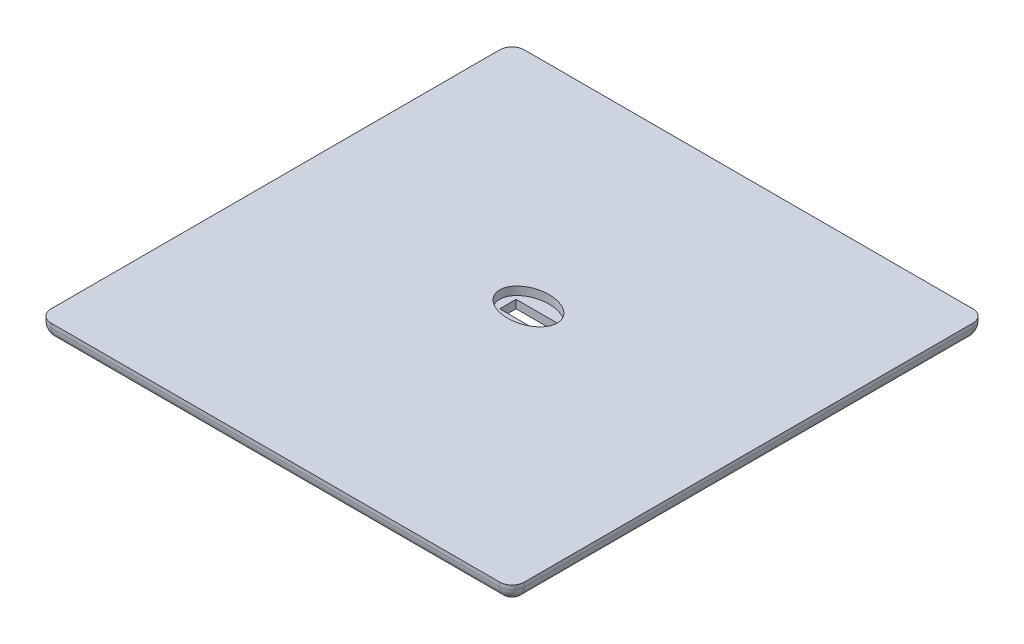
SolidWorks part; units mm, degrees
ref_plane "Front Plane" through (0, 0, 0) normal (0, 0, 1) x (1, 0, 0)
ref_plane "Top Plane" through (0, 0, 0) normal (0, 1, 0) x (1, 0, 0)
ref_plane "Right Plane" through (0, 0, 0) normal (1, 0, 0) x (0, 0, -1)
sketch "Sketch7" plane through (0, 0, 0) normal (0, 0, 1) x (1, 0, 0)
  line L0 (55, 0) -> (-55, 0) construction
  line L1 (-47.5, 4) -> (47.5, 4)
  line L2 (-47.5, 4) -> (-47.5, 0)
  line L3 (-47.5, 0) -> (47.5, 0)
  line L4 (47.5, 4) -> (47.5, 0)
  point P6 (0, 0)
  point P7 (0, 0)
  point P8 (0, 0)
  point P9 (0, 0)
  point P10 (0, 0)
  point P11 (0, 0)
extrude "Boss-Extrude4" add sketch "Sketch7" along normal blind 47.5 and the other way blind 47.5
sketch "Sketch8" plane through (0, 0, 0) normal (0, 0, 1) x (1, 0, 0)
  line L1 (-52.5, 4) -> (52.5, 4)
  line L2 (-52.5, 4) -> (-52.5, 8)
  line L3 (-52.5, 8) -> (52.5, 8)
  line L4 (52.5, 4) -> (52.5, 8)
  point P4 (0, 0)
  point P5 (0, 0)
  point P6 (0, 0)
  point P7 (0, 0)
  point P8 (0, 0)
  point P9 (0, 0)
  point P10 (0, 0)
extrude "Boss-Extrude5" add sketch "Sketch8" along normal blind 52.5 and the other way blind 52.5
sketch "Sketch9" plane through (0, 0, 0) normal (0, 0, 1) x (1, 0, 0)
  line L1 (-57.5, 12) -> (57.5, 12)
  line L2 (-57.5, 12) -> (-57.5, 8)
  line L3 (-57.5, 8) -> (57.5, 8)
  line L4 (57.5, 12) -> (57.5, 8)
  point P4 (0, 0)
  point P5 (0, 0)
  point P6 (0, 0)
  point P7 (0, 0)
  point P8 (0, 0)
  point P9 (0, 0)
  point P10 (0, 0)
  point P11 (0, 0)
  point P12 (0, 0)
  point P13 (0, 0)
extrude "Boss-Extrude6" add sketch "Sketch9" along normal blind 57.5 and the other way blind 57.5
sketch "Sketch10" plane through (0, 0, 0) normal (0, 1, 0) x (1, 0, 0)
  line L1 (-42.5, 42.5) -> (42.5, 42.5)
  line L2 (-42.5, 42.5) -> (-42.5, -42.5)
  line L3 (-42.5, -42.5) -> (42.5, -42.5)
  line L4 (42.5, 42.5) -> (42.5, -42.5)
  point P4 (0, 0)
  point P5 (0, 0)
  point P6 (0, 0)
extrude "Cut-Extrude1" cut sketch "Sketch10" against normal blind 3.5 and the other way blind 8
sketch "Sketch12" plane through (0, 12, 0) normal (0, 1, 0) x (1, 0, 0)
  ellipse E0 centre (0, 4) end of major axis (7, 4) minor radius 5
extrude "Cut-Extrude2" cut sketch "Sketch12" against normal blind 2
sketch "Sketch13" plane through (0, 0, 0) normal (0, 1, 0) x (1, 0, 0)
  line L1 (-5, 6) -> (5, 6)
  line L2 (-5, 6) -> (-5, 2)
  line L3 (-5, 2) -> (5, 2)
  line L4 (5, 6) -> (5, 2)
  point P4 (0, 0)
  point P5 (0, 0)
  point P6 (0, 0)
  point P7 (0, 0)
extrude "Cut-Extrude3" cut sketch "Sketch13" against normal through all and the other way blind 29
fillet "Fillet4" radius 3 24 edges at (-47.5, 2, -47.5) (-52.5, 6, -52.5) (-57.5, 10, -57.5) (-47.5, 0, 0) (-52.5, 4, 0) (-57.5, 8, 0) (-57.5, 10, 57.5) (-52.5, 6, 52.5) (-47.5, 2, 47.5) (0, 8, -57.5) (0, 4, -52.5) (0, 0, -47.5) (47.5, 2, -47.5) (52.5, 6, -52.5) (57.5, 10, -57.5) (57.5, 10, 57.5) (0, 8, 57.5) (57.5, 8, 0) (52.5, 4, 0) (0, 4, 52.5) (52.5, 6, 52.5) (47.5, 2, 47.5) (47.5, 0, 0) (0, 0, 47.5)
